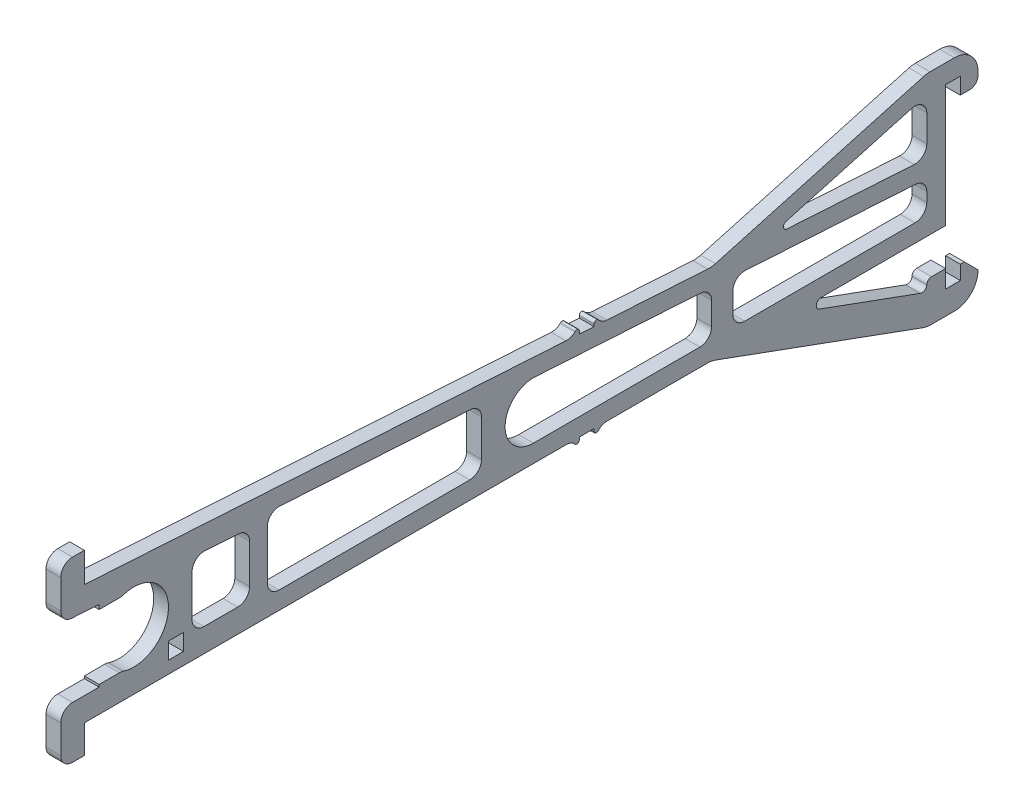
SolidWorks part; units mm, degrees
material "Delrin"
ref_plane "Front Plane" through (0, 0, 0) normal (0, 0, 1) x (1, 0, 0)
ref_plane "Top Plane" through (0, 0, 0) normal (0, 1, 0) x (1, 0, 0)
ref_plane "Right Plane" through (0, 0, 0) normal (1, 0, 0) x (0, 0, -1)
sketch "Sketch1" plane through (0, 0, 0) normal (1, 0, 0) x (0, 0, -1)
  line L0 (0.3859, 6.2619) -> (62.1851, 2.453)
  line L1 (0, -6.2738) -> (62.1851, -6.2738)
  line L2 (85.344, 8.8996) -> (88.3158, 8.8996)
  line L3 (12.4587, 2.973) -> (0.2297, 3.7267)
  line L4 (12.4587, -3.7338) -> (0, -3.7338)
  line L5 (-5.3213, -3.7338) -> (-7.8613, -3.7338)
  line L6 (45.3857, 3.4884) -> (45.3857, 1.5834) construction
  line L7 (85.344, -6.2738) -> (85.344, 8.8996) construction
  line L8 (-5.3213, -0.4002) -> (-5.3213, 21.638) construction
  line L9 (0.3859, 6.2619) -> (-5.3213, 6.6137)
  line L10 (-5.3213, 6.6137) -> (-5.3213, 9.8134)
  line L11 (-5.3213, 9.8134) -> (-7.8613, 9.8134)
  line L12 (-7.8613, 9.8134) -> (-7.8613, 4.2254)
  line L13 (14.3637, 3.4954) -> (14.3637, 5.4004) construction
  line L14 (0, -6.2738) -> (-5.3213, -6.2738)
  line L15 (-5.3213, -6.2738) -> (-5.3213, -9.3218)
  line L16 (14.3637, 3.4954) -> (14.3637, -4.3688)
  line L17 (39.3251, 1.9569) -> (39.3251, -4.3688)
  line L18 (37.4201, 2.0744) -> (37.4201, -4.3688)
  line L19 (-5.3213, -9.3218) -> (-7.8613, -9.3218)
  line L20 (-7.8613, -9.3218) -> (-7.8613, -3.7338)
  line L21 (45.3857, -4.3688) -> (45.3857, -6.2738) construction
  line L22 (12.4587, 2.973) -> (12.4587, -3.7338)
  line L23 (0, 3.7338) -> (0, -3.7338)
  line L24 (89.9668, 5.0896) -> (88.9508, 5.0896)
  line L25 (88.9508, 5.0896) -> (88.9508, 6.8676)
  line L26 (88.9508, 6.8676) -> (87.376, 6.8676)
  line L27 (87.376, 6.8676) -> (87.376, -6.2738)
  line L28 (87.376, -12.1824) -> (88.9508, -12.1824)
  line L29 (88.9508, -12.1824) -> (88.9508, -10.6584)
  line L30 (88.9508, -10.6584) -> (89.3826, -10.6584)
  line L31 (90.8558, -12.1316) -> (90.8558, -12.1824)
  line L32 (88.3158, -14.7224) -> (85.344, -14.7224)
  line L33 (85.344, -14.7224) -> (85.344, -6.2738) construction
  line L34 (90.8558, 5.9786) -> (90.8558, 6.3596)
  line L35 (89.3826, -10.6584) -> (90.8558, -12.1316)
  line L36 (64.4711, 0.4071) -> (64.4711, -4.3688)
  line L37 (62.1851, 0.548) -> (62.1851, -4.3688)
  line L38 (62.1851, 2.453) -> (85.344, 8.8996)
  line L39 (68.0011, 2.0945) -> (85.344, 6.9222)
  line L40 (62.1851, -6.2738) -> (85.344, -14.7224)
  line L41 (71.0788, -6.2738) -> (85.344, -11.4779)
  line L42 (63.2297, -3.4104) -> (86.3886, -11.859) construction
  line L43 (62.696, 0.6178) -> (85.8549, 7.0644) construction
  line L44 (71.0788, -6.2738) -> (85.344, -6.2738)
  line L45 (-1.3313, 3.4884) -> (-3.7338, 3.4884)
  line L46 (68.0011, 2.0945) -> (85.344, 1.0256)
  line L47 (62.1851, -4.3688) -> (62.1851, 49995.6312) construction
  line L48 (85.344, 6.9222) -> (85.344, 1.0256)
  line L49 (85.344, -0.8794) -> (85.344, -4.3688)
  line L50 (87.376, -12.1824) -> (87.376, -10.2774)
  line L51 (85.344, -6.2738) -> (87.376, -6.2738)
  line L52 (87.376, -10.2774) -> (85.344, -10.2774)
  line L53 (85.344, -10.2774) -> (85.344, -11.4779)
  line L54 (14.3637, 3.4954) -> (37.4201, 2.0744)
  line L55 (14.3637, -4.3688) -> (37.4201, -4.3688)
  line L56 (39.3251, -4.3688) -> (62.1851, -4.3688)
  line L57 (39.3251, 1.9569) -> (62.1851, 0.548)
  line L58 (64.4711, 0.4071) -> (85.344, -0.8794)
  line L59 (64.4711, -4.3688) -> (85.344, -4.3688)
  line L60 (-3.7338, 0) -> (-3.7338, 17.9839) construction
  line L61 (-3.7338, 3.971) -> (-7.8613, 4.2254)
  line L62 (-3.7338, -3.7338) -> (-5.3213, -3.7338)
  line L63 (-3.7338, 3.4884) -> (-3.7338, 3.971)
  line L64 (-1.3313, -3.4884) -> (-3.7338, -3.4884)
  line L65 (-3.7338, -3.4884) -> (-3.7338, -3.7338)
  line L66 (6.2738, 3.3542) -> (6.2738, -3.7338)
  line L67 (3.7338, 0) -> (3.7338, 11.926) construction
  arc A0 (0, -3.7338) -> (0, 3.7338) centre (0, 0) ccw
  circle A1 centre (0, 0) radius 6.2738 construction
  arc A2 (88.3158, 8.8996) -> (90.8558, 6.3596) centre (88.3158, 6.3596) cw
  arc A3 (90.8558, -12.1824) -> (88.3158, -14.7224) centre (88.3158, -12.1824) cw
  arc A4 (90.8558, 5.9786) -> (89.9668, 5.0896) centre (89.9668, 5.9786) cw
  arc A5 (0, 3.7338) -> (-1.3313, 3.4884) centre (0, 0) ccw
  circle A6 centre (0, 0) radius 3.7338 construction
  arc A7 (-1.3313, -3.4884) -> (0, -3.7338) centre (0, 0) ccw
  point P47 (90.8558, 8.8996)
  point P50 (90.8558, -14.7224)
  point P53 (90.8558, 5.0896)
  point P54 (90.8558, -10.6584)
  point P56 (90.8558, -10.6584)
  point P79 (3.5707, 1.0917)
  dimension "D1" = 7.4676
  dimension "D2" = 2.54
  dimension "D3" = 5.842
  dimension "D8" = 1.5748
  dimension "D18" = 2.54
  dimension "D19" = 2.54
  dimension "D20" = 0.889
  dimension "D21" = 22.86
  dimension "D5" = 37.4201
  dimension "D10" = 1.905
  dimension "D11" = 1.778
  dimension "D12" = 1.905
  dimension "D4" = 5.3842
  dimension "D9" = 1.5748
  dimension "D14" = 1.524
  dimension "D15" = 3.81
  dimension "D16" = 4.064
  dimension "D17" = 1.905
  dimension "D22" = 19.05
  dimension "D23" = 85.344
  dimension "D24" = 2.032
  dimension "D25" = 2.286
  dimension "D29" = 1.905
  dimension "D13" = 2.54
  dimension "D30" = 5.588
  dimension "D31" = 1.905
  dimension "D32" = 17.78
  dimension "D33" = 1.5875
  dimension "D6" = 1.905
  dimension "D7" = 0.4826
  dimension "D34" = 2.54
  dimension "D27" = 3.048
  dimension "D28" = 1.905
extrude "Boss-Extrude1" add sketch "Sketch1" along normal blind 1.5875 contours A1 A0 | A4 L34 A2 L2 L38 L0 L9 L10 L11 L12 L49 L20 L19 L15 L14 L1 L40 L32 A3 L31 L35 L30 L29 L28 L50 L52 L53 L41 L44 L51 L27 L26 L25 L24 | L18 L17 | L22 L16 | L37 L36 region at (0, 3.3422, -31.2229) region at (0, -0.1773, -4.5129)
fillet "Fillet1" radius 2.54 4 edges at (0.7937, 2.453, -62.1851) (0.7937, 8.8996, -85.344) (0.7937, -6.2738, -62.1851) (0.7937, -14.7224, -85.344)
fillet "Fillet2" radius 1.27 16 edges at (0.7937, 1.0256, -85.344) (0.7937, 6.9222, -85.344) (0.7937, -4.3688, -14.3637) (0.7937, 3.4954, -14.3637) (0.7937, 2.0744, -37.4201) (0.7937, -4.3688, -37.4201) (0.7937, -4.3688, -64.4711) (0.7937, 0.4071, -64.4711) (0.7937, -4.3688, -85.344) (0.7937, -0.8794, -85.344) (0.7937, -4.3688, -62.1851) (0.7937, 0.548, -62.1851) (0.7937, -3.7338, -6.2738) (0.7937, 3.3542, -6.2738) (0.7937, -3.7338, -12.4587) (0.7937, 2.973, -12.4587)
fillet "Fillet3" radius 0.508 2 edges at (0.7937, -6.2738, -71.0788) (0.7937, -11.4779, -85.344)
fillet "Fillet4" radius 0.508 1 edges at (0.7937, -10.2774, -85.344)
sketch "Sketch4" plane through (1.5875, 0, 0) normal (1, 0, 0) x (0, 0, -1)
  line L0 (39.3251, 1.9569) -> (60.9932, 0.6215) construction
  line L1 (39.3251, -4.3688) -> (60.9151, -4.3688) construction
  line L2 (39.9601, -1.3223) -> (39.3251, -1.3223) construction
  line L6 (39.3251, 1.9569) -> (39.3251, -4.3688) construction
  line L7 (39.3251, 1.9569) -> (43.194, 1.7185)
  line L8 (39.3251, 1.9569) -> (39.3251, -4.3688)
  line L9 (39.3251, -4.3688) -> (43.0066, -4.3688)
  arc A0 (43.194, 1.7185) -> (43.0066, -4.3688) centre (43.0066, -1.3223) ccw
  dimension "D1" = 0.635
sketch "Sketch6" plane through (1.5875, 0, 0) normal (-1, 0, 0) x (0, 0, 1)
  line L0 (-47.0577, -6.2738) -> (-47.9467, -7.1628)
  line L1 (5.3213, 6.6137) -> (-61.759, 2.4793) construction
  line L2 (-47.9467, -17.1193) -> (-47.9467, 10.2613) construction
  line L3 (-47.9467, -7.1628) -> (-47.9467, -6.2738)
  line L4 (-47.9467, -6.2738) -> (-47.0577, -6.2738)
  line L5 (-61.7363, -6.2738) -> (5.3213, -6.2738) construction
  line L6 (-48.7404, -10.0838) -> (-48.7404, 6.4573) construction
  line L7 (-49.5342, -10.0838) -> (-47.9467, -10.0838) construction
  line L8 (-49.5342, -6.2738) -> (-50.4232, -6.2738)
  line L9 (-49.5342, -7.1628) -> (-49.5342, -6.2738)
  line L10 (-50.4232, -6.2738) -> (-49.5342, -7.1628)
  line L11 (-50.4215, 3.178) -> (-49.5342, 4.1217)
  line L13 (-49.5342, -17.1193) -> (-49.5342, 10.2613) construction
  line L14 (-49.5342, 4.1217) -> (-49.5342, 3.2327)
  line L15 (-49.5342, 3.2327) -> (-50.4215, 3.178)
  line L16 (-47.9467, 3.3306) -> (-47.0594, 3.3853)
  line L17 (-47.0594, 3.3853) -> (-47.9467, 4.2196)
  line L18 (-47.9467, 4.2196) -> (-47.9467, 3.3306)
  dimension "D1" = 0.889
extrude "Boss-Extrude3" add sketch "Sketch6" along normal up to surface (1.5875 mm away) contours L4 L3 L0 | L8 L10 L9 | L15 L14 L11 | L17 L18 L16 | L18 L17 L16 | L14 L15 L11 | L10 L8 L9 | L3 L4 L0 region at (1.5875, -6.5701, -47.6504) region at (1.5875, -6.5701, -49.8305) region at (1.5875, 3.5108, -49.83) region at (1.5875, 3.6451, -47.6509) up to face at (0, -2.7746, -54.7441)
fillet "Fillet5" radius 1.27 4 edges at (0.7937, 3.178, -50.4215) (0.7937, 3.3853, -47.0594) (0.7937, -6.2738, -50.4232) (0.7937, -6.2738, -47.0577)
fillet "Fillet6" radius 0.254 4 edges at (0.7937, -7.1628, -49.5342) (0.7937, -7.1628, -47.9467) (0.7937, 4.2196, -47.9467) (0.7937, 4.1217, -49.5342)
extrude "Boss-Extrude4" add sketch "Sketch4" against normal up to surface (1.5875 mm away) up to face at (0, -2.3687, -52.8385)
sketch "Sketch5" plane through (1.5875, 0, 0) normal (1, 0, 0) x (0, 0, -1)
  line L0 (3.7592, -3.175) -> (3.7592, -3.683) construction
  line L1 (3.7592, -4.445) -> (3.7592, -3.683) construction
  line L2 (3.7592, -4.445) -> (3.7592, -4.953) construction
  line L3 (5.3467, -4.445) -> (5.3467, -3.683) construction
  line L4 (5.3467, -4.953) -> (5.3467, -4.445) construction
  line L5 (5.3467, -3.683) -> (5.3467, -3.175) construction
  line L6 (5.3467, -3.175) -> (3.7592, -3.175) construction
  line L7 (3.7592, -4.953) -> (5.3467, -4.953) construction
  line L8 (3.7592, -3.175) -> (3.7592, -3.683)
  line L9 (3.7592, -4.445) -> (3.7592, -3.683)
  line L10 (3.7592, -4.445) -> (3.7592, -4.953)
  line L11 (5.3467, -4.445) -> (5.3467, -3.683)
  line L12 (5.3467, -4.953) -> (5.3467, -4.445)
  line L13 (5.3467, -3.683) -> (5.3467, -3.175)
  line L14 (5.3467, -3.175) -> (3.7592, -3.175)
  line L15 (3.7592, -4.953) -> (5.3467, -4.953)
extrude "Cut-Extrude1" cut sketch "Sketch5" against normal up to next
fillet "Fillet8" radius 1.27 4 edges at (0.7937, 9.8134, 7.8613) (0.7937, -9.3218, 7.8613) (0.7937, -3.7338, 7.8613) (0.7937, 4.2254, 7.8613)
fillet "Fillet9" radius 1.27 2 edges at (0.7937, -3.4884, 1.3313) (0.7937, 3.4884, 1.3313)
fillet "Fillet10" radius 0.381 1 edges at (0.7937, 2.0945, -68.0011)
